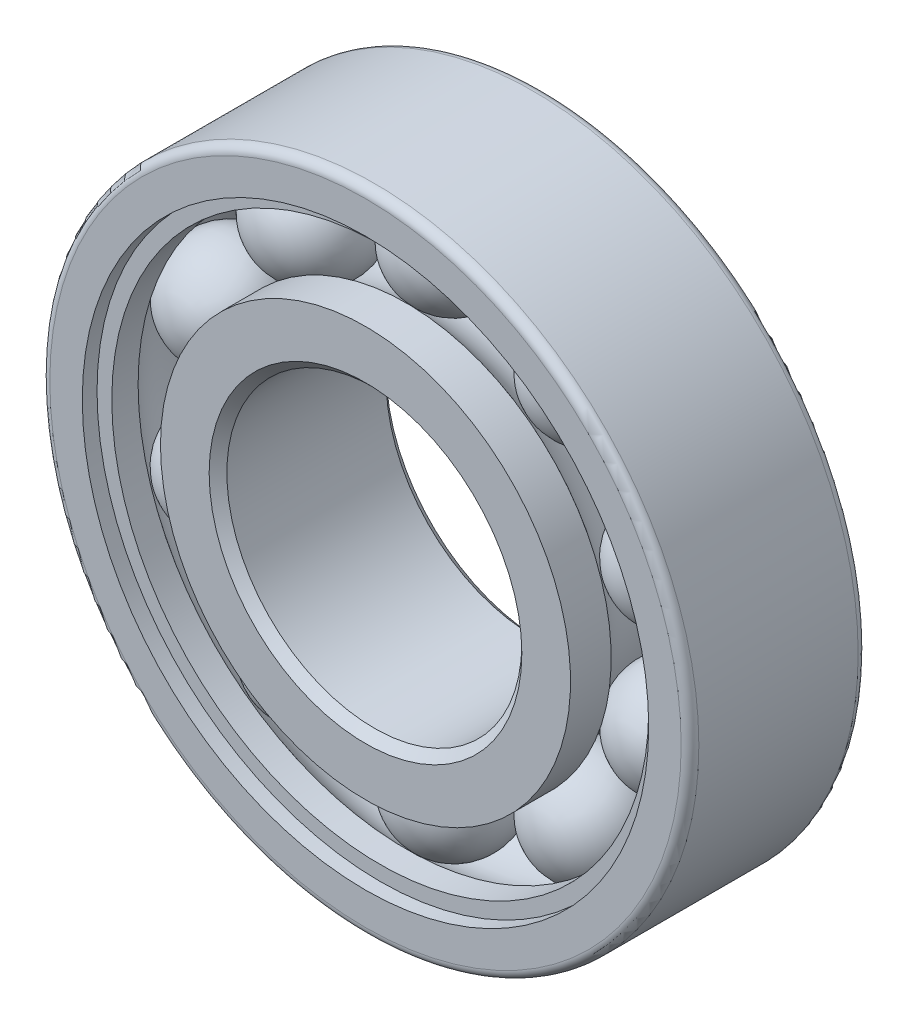
SolidWorks part; units mm, degrees
ref_plane "Front Plane" through (0, 0, 0) normal (0, 0, 1) x (1, 0, 0)
ref_plane "Top Plane" through (0, 0, 0) normal (0, 1, 0) x (1, 0, 0)
ref_plane "Right Plane" through (0, 0, 0) normal (1, 0, 0) x (0, 0, -1)
sketch "Sketch6" plane through (0, 0, 0) normal (1, 0, 0) x (0, 0, -1)
  line L0 (0, 10.05) -> (0, 0) construction
  line L1 (3, 11) -> (-3, 11)
  line L2 (3, 11) -> (3, 9.1)
  line L3 (3, 9.1) -> (-3, 9.1)
  line L4 (-3, 11) -> (-3, 9.1)
  line L5 (3, 11) -> (-3, 9.1) construction
  line L6 (3, 9.1) -> (-3, 11) construction
  line L7 (3, 6.95) -> (-3, 6.95)
  line L8 (3, 6.95) -> (3, 5)
  line L9 (3, 5) -> (-3, 5)
  line L10 (-3, 6.95) -> (-3, 5)
  line L11 (3, 6.95) -> (-3, 5) construction
  line L12 (3, 5) -> (-3, 6.95) construction
  line L13 (0, 0) -> (-4.8837, 0) construction
  circle A0 centre (0, 8.015) radius 1.9401
  point P0 (0, 10.05)
  point P5 (0, 5.975)
  point P15 (0, 0)
  dimension "D1" = 6
  dimension "D2" = 5
  dimension "D3" = 11
  dimension "D4" = 6.95
  dimension "D5" = 9.1
revolve "Revolve2" add sketch "Sketch6" angle 360 about L13 region at (0, 10.1727, 0) region at (0, 5.8479, 0)
ref_axis "Axis1" through (0, 0, 3) along (0, 0, -1)
sketch "Sketch9" plane through (0, 0, 0) normal (1, 0, 0) x (0, 0, -1)
  line L0 (-1.9, 8.01) -> (1.9, 8.01)
  circle A0 centre (0, 8.01) radius 1.9
  point P4 (0, 0)
  dimension "D1" = 8.01
  dimension "D2" = 3.8
revolve "Revolve3" add sketch "Sketch9" angle 360 about L0 region at (0, 8.8164, 0)
pattern_circular "CirPattern3" count 10 over 360 about axis through (0, 0, 3) along (0, 0, -1) of bodies 104
sketch "Sketch10" plane through (0, 0, -3) normal (0, 0, -1) x (-1, 0, 0)
  circle A0 centre (0, 0) radius 9.1 construction
  circle A1 centre (0, 0) radius 9.1
  circle A2 centre (0, 0) radius 9.6
  dimension "D1" = 0.5
extrude "Cut-Extrude1" cut sketch "Sketch10" against normal blind 0.5
mirror "Mirror1" about plane through (0, 0, 0) normal (0, 0, 1) of "Cut-Extrude1"
fillet "Fillet1" radius 0.3 2 edges at (-11, 0, -3) (-11, 0, 3)
chamfer "Chamfer1" distance 0.3 angle 45 2 edges at (-5, 0, -3) (-5, 0, 3)
